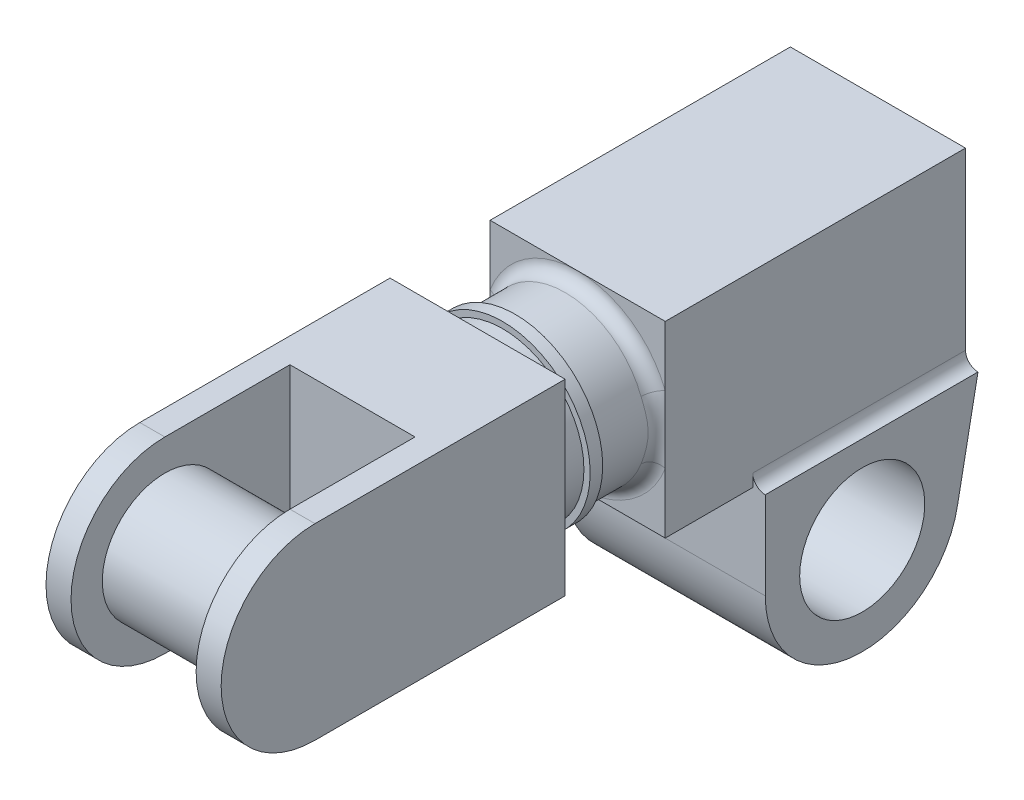
SolidWorks part; units mm, degrees
material "Cast Carbon Steel"
ref_plane "Front Plane" through (0, 0, 0) normal (0, 0, 1) x (1, 0, 0)
ref_plane "Top Plane" through (0, 0, 0) normal (0, 1, 0) x (1, 0, 0)
ref_plane "Right Plane" through (0, 0, 0) normal (1, 0, 0) x (0, 0, -1)
sketch "Sketch1" plane through (0, 0, 0) normal (0, 0, 1) x (1, 0, 0)
  line L1 (-70, 75) -> (70, 75)
  line L2 (-70, 75) -> (-70, -75)
  line L3 (-70, -75) -> (70, -75)
  line L4 (70, 75) -> (70, -75)
  line L5 (-70, 75) -> (70, -75) construction
  line L6 (-70, -75) -> (70, 75) construction
  point P0 (0, 0)
  dimension "D1" = 150
  dimension "D2" = 140
extrude "Boss-Extrude1" add sketch "Sketch1" along normal blind 240
sketch "Sketch2" plane through (0, 0, 240) normal (0, 0, 1) x (1, 0, 0)
  circle A0 centre (0, 0) radius 65
  dimension "D1" = 130
extrude "Boss-Extrude2" add sketch "Sketch2" along normal blind 50
sketch "Sketch3" plane through (0, 0, 290) normal (0, 0, 1) x (1, 0, 0)
  circle A0 centre (0, 0) radius 70
  dimension "D1" = 140
extrude "Boss-Extrude3" add sketch "Sketch3" along normal blind 10
sketch "Sketch7" plane through (0, 0, 0) normal (1, 0, 0) x (0, 0, -1)
  line L0 (-240, -75) -> (0, -75) construction
  line L1 (0, -75) -> (-170.0448, -75)
  line L4 (0, -75) -> (-16.2188, -158.4383)
  line L5 (-170.0448, -145) -> (-170.0448, -75)
  arc A2 (-16.2188, -158.4383) -> (-170.0448, -145) centre (-92.5448, -145) cw
  circle A3 centre (-92.5448, -145) radius 50
  dimension "D1" = 100
  dimension "D2" = 77.5
  dimension "D6" = 170.0448
  dimension "D3" = 83.4383
  dimension "D4" = 70
  dimension "D5" = 70
  dimension "D7" = 92.5448
extrude "Boss-Extrude5" add sketch "Sketch7" along normal mid plane 160
fillet "Fillet1" radius 10 3 edges at (70, -75, 85.0224) (65, 0, 240) (-70, -75, 85.0224)
sketch "Sketch8" plane through (0, 0, 300) normal (0, 0, 1) x (1, 0, 0)
  circle A0 centre (0, 0) radius 65
  dimension "D1" = 130
extrude "Boss-Extrude6" add sketch "Sketch8" along normal blind 20
sketch "Sketch10" plane through (0, 0, 0) normal (1, 0, 0) x (0, 0, -1)
  line L0 (-520, 75) -> (-320, 75)
  line L1 (-520, -75) -> (-320, -75)
  line L2 (-320, -75) -> (-320, 75)
  line L3 (-320, 65) -> (-320, -65) construction
  arc A0 (-520, 75) -> (-520, -75) centre (-520, 0) ccw
  dimension "D1" = 150
  dimension "D2" = 200
extrude "Boss-Extrude7" add sketch "Sketch10" along normal mid plane 140
sketch "Sketch12" plane through (0, 0, 0) normal (1, 0, 0) x (0, 0, -1)
  line L0 (-520, 75) -> (-420, 75)
  line L1 (-320, 75) -> (-520, 75) construction
  line L2 (-420, 75) -> (-420, -75)
  line L3 (-520, -75) -> (-320, -75) construction
  line L4 (-420, -75) -> (-520, -75)
  arc A0 (-520, 75) -> (-520, -75) centre (-520, 0) ccw construction
  arc A1 (-520, 75) -> (-520, -75) centre (-520, 0) ccw
extrude "Cut-Extrude1" cut sketch "Sketch12" against normal mid plane 100
sketch "Sketch14" plane through (50, 0, 0) normal (-1, 0, 0) x (0, 0, 1)
  circle A0 centre (520, 0) radius 50
extrude "Boss-Extrude8" add sketch "Sketch14" along normal up to next
